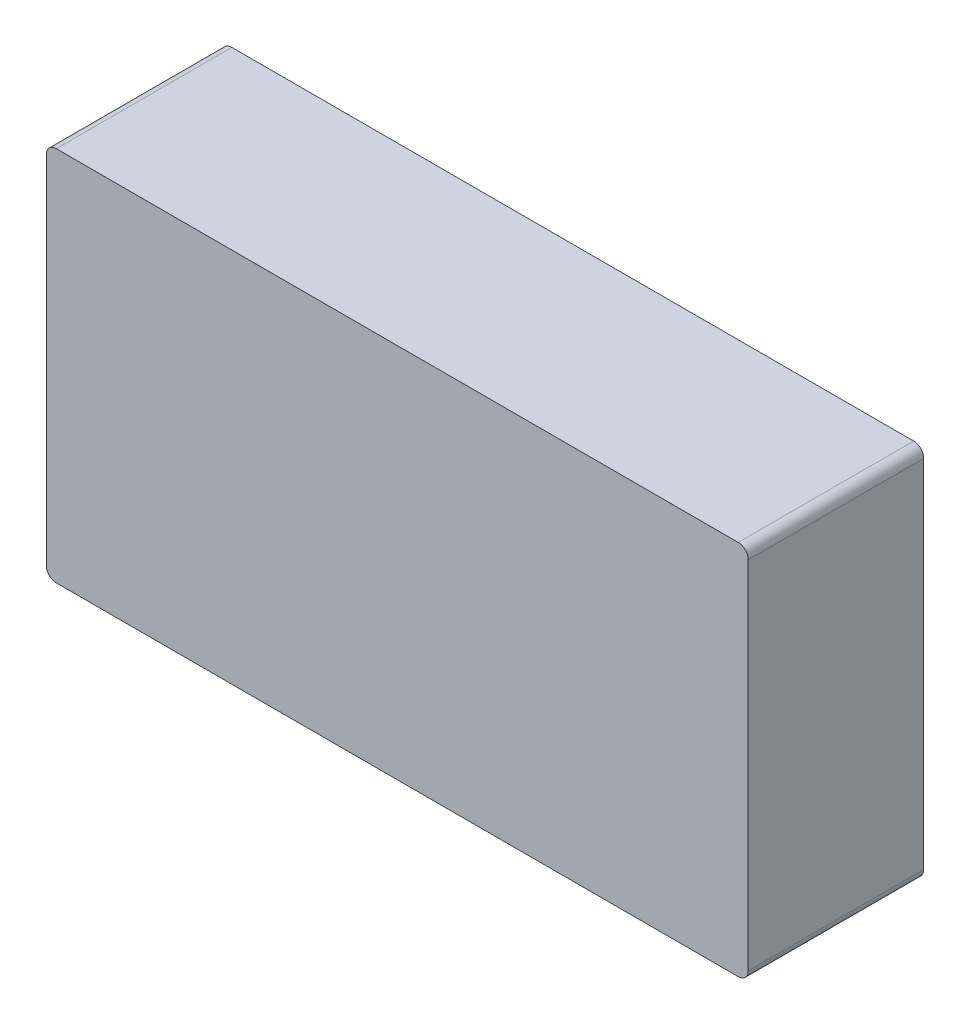
SolidWorks part; units mm, degrees
ref_plane "前视基准面" through (0, 0, 0) normal (0, 0, 1) x (1, 0, 0)
ref_plane "上视基准面" through (0, 0, 0) normal (0, 1, 0) x (1, 0, 0)
ref_plane "右视基准面" through (0, 0, 0) normal (1, 0, 0) x (0, 0, -1)
other "Configuration Table"
sketch "Sketch1" plane through (0, 0, 0) normal (0, 0, 1) x (1, 0, 0)
  line L1 (-70, -37.5) -> (70, -37.5)
  line L2 (-70, -37.5) -> (-70, 37.5)
  line L3 (-70, 37.5) -> (70, 37.5)
  line L4 (70, -37.5) -> (70, 37.5)
  line L5 (-70, -37.5) -> (70, 37.5) construction
  line L6 (-70, 37.5) -> (70, -37.5) construction
  point P0 (0, 0)
extrude "Boss-Extrude1" add sketch "Sketch1" along normal blind 35
shell "Shell1" thickness 2.5 removed face at (0, 0, 0)
ref_plane "Plane1" through (0, 0, 35) normal (0, 0, 1) x (1, 0, 0)
sketch "Sketch3" plane through (0, 0, 35) normal (0, 0, 1) x (1, 0, 0)
  line L1 (-10, -5) -> (10, -5)
  line L2 (-10, -5) -> (-10, 5)
  line L3 (-10, 5) -> (10, 5)
  line L4 (10, -5) -> (10, 5)
  line L5 (-10, -5) -> (10, 5) construction
  line L6 (-10, 5) -> (10, -5) construction
  point P0 (0, 0)
sketch "Sketch4" plane through (0, 0, 35) normal (0, 0, 1) x (1, 0, 0)
  circle A0 centre (60, 27.5) radius 1.6
  circle A1 centre (-60, 27.5) radius 1.6
  circle A2 centre (-60, -27.5) radius 1.6
  circle A3 centre (60, -27.5) radius 1.6
fillet "Fillet1" radius 2 4 edges at (70, -37.5, 17.5) (-70, -37.5, 17.5) (-70, 37.5, 17.5) (70, 37.5, 17.5)
ref_plane "face_bottom_mating" through (0, 0, 32.5) normal (0, 0, 1) x (1, 0, 0)
ref_plane "face_top_outer" through (0, 0, 35) normal (0, 0, 1) x (1, 0, 0)
sketch3d "3DSketch1"
  line L0 (60, 27.5, 0) -> (60, 27.5, 35) construction
ref_axis "axis_screw_hole_1" through (60, 27.5, 0) along (0, 0, 1)
sketch3d "3DSketch2"
  line L0 (-60, 27.5, 0) -> (-60, 27.5, 35) construction
ref_axis "axis_screw_hole_2" through (-60, 27.5, 0) along (0, 0, 1)
sketch3d "3DSketch3"
  line L0 (-60, -27.5, 0) -> (-60, -27.5, 35) construction
ref_axis "axis_screw_hole_3" through (-60, -27.5, 0) along (0, 0, 1)
sketch3d "3DSketch4"
  line L0 (60, -27.5, 0) -> (60, -27.5, 35) construction
ref_axis "axis_screw_hole_4" through (60, -27.5, 0) along (0, 0, 1)
